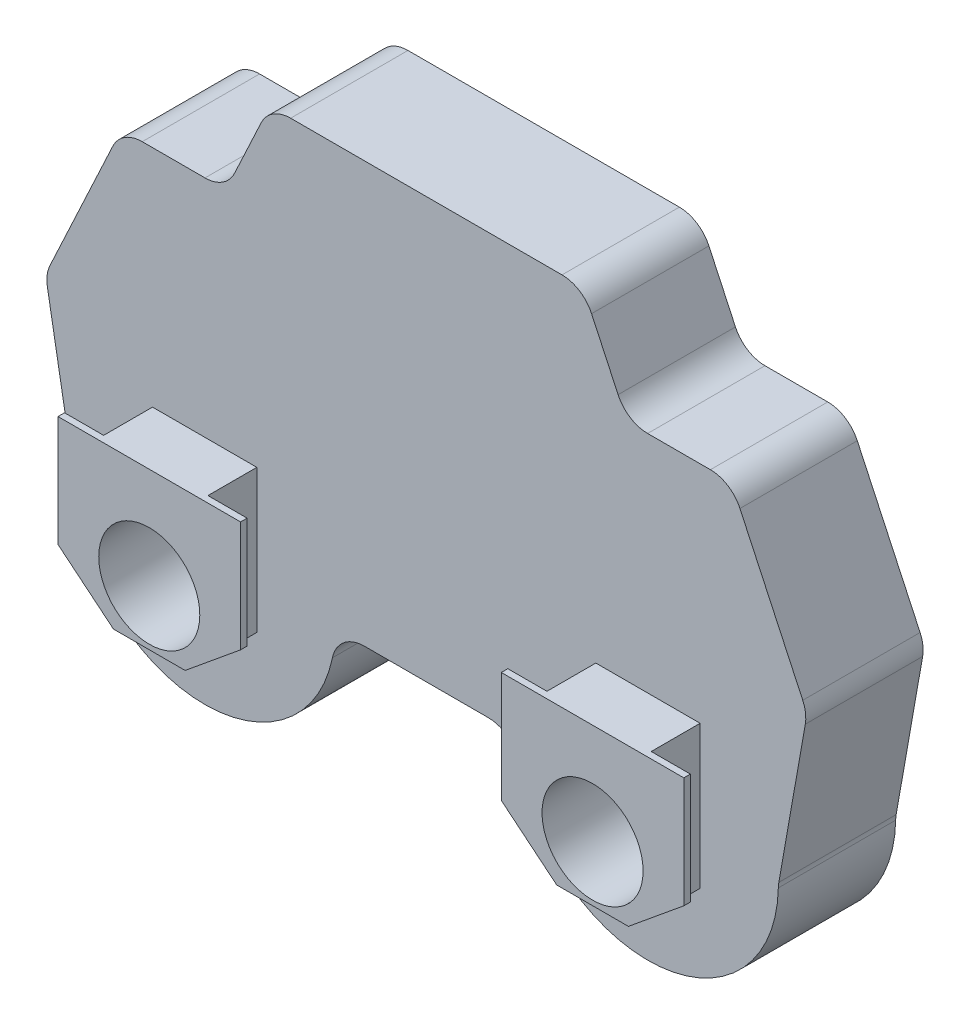
SolidWorks part; units mm, degrees
ref_plane "Alzado" through (0, 0, 0) normal (0, 0, 1) x (1, 0, 0)
ref_plane "Planta" through (0, 0, 0) normal (0, 1, 0) x (1, 0, 0)
ref_plane "Vista lateral" through (0, 0, 0) normal (1, 0, 0) x (0, 0, -1)
sketch "Croquis1" plane through (0, 0, 0) normal (0, 0, 1) x (1, 0, 0)
  line L0 (-9.5051, 0) -> (9.5051, 0)
  line L1 (54.0717, 0.4066) -> (58.1344, 23.4475)
  line L2 (57.7419, 26.4288) -> (48.1081, 47.0886)
  line L3 (43.5765, 49.9755) -> (33.9472, 49.9755)
  line L4 (29.4157, 52.8624) -> (25.3462, 61.5895)
  line L5 (20.8146, 64.4765) -> (-20.8146, 64.4765)
  line L6 (0, 64.4765) -> (0, 0) construction
  line L7 (-29.4157, 52.8624) -> (-25.3462, 61.5895)
  line L8 (-43.5765, 49.9755) -> (-33.9472, 49.9755)
  line L9 (-57.7419, 26.4288) -> (-48.1081, 47.0886)
  line L10 (-54.0717, 0.4066) -> (-58.1344, 23.4475)
  arc A0 (14.4041, -4) -> (53.9966, -0.3693) centre (34, 0) ccw
  arc A1 (58.1344, 23.4475) -> (57.7419, 26.4288) centre (53.2104, 24.3157) ccw
  arc A2 (48.1081, 47.0886) -> (43.5765, 49.9755) centre (43.5765, 44.9755) ccw
  arc A3 (33.9472, 49.9755) -> (29.4157, 52.8624) centre (33.9472, 54.9755) cw
  arc A4 (53.9966, -0.3693) -> (54.0717, 0.4066) centre (58.9957, -0.4616) cw
  arc A5 (9.5051, 0) -> (14.4041, -4) centre (9.5051, -5) cw
  arc A6 (25.3462, 61.5895) -> (20.8146, 64.4765) centre (20.8146, 59.4765) ccw
  circle A7 centre (34, 0) radius 5.5
  circle A8 centre (-34, 0) radius 5.5
  arc A9 (-25.3462, 61.5895) -> (-20.8146, 64.4765) centre (-20.8146, 59.4765) cw
  arc A10 (-9.5051, 0) -> (-14.4041, -4) centre (-9.5051, -5) ccw
  arc A11 (-53.9966, -0.3693) -> (-54.0717, 0.4066) centre (-58.9957, -0.4616) ccw
  arc A12 (-33.9472, 49.9755) -> (-29.4157, 52.8624) centre (-33.9472, 54.9755) ccw
  arc A13 (-48.1081, 47.0886) -> (-43.5765, 49.9755) centre (-43.5765, 44.9755) cw
  arc A14 (-58.1344, 23.4475) -> (-57.7419, 26.4288) centre (-53.2104, 24.3157) cw
  arc A15 (-14.4041, -4) -> (-53.9966, -0.3693) centre (-34, 0) cw
  point P15 (58.4082, 25)
  point P18 (46.7619, 49.9755)
  point P21 (30.7619, 49.9755)
  point P24 (54, 0)
  point P27 (14, 0)
  point P30 (24, 64.4765)
  point P49 (-24, 64.4765)
  point P50 (-14, 0)
  point P51 (-54, 0)
  point P52 (-30.7619, 49.9755)
  point P53 (-46.7619, 49.9755)
  point P54 (-58.4082, 25)
  dimension "D1" = 20
  dimension "D11" = 5
  dimension "D12" = 5
  dimension "D13" = 5
  dimension "D14" = 5
  dimension "D15" = 11
  dimension "D2" = 25
  dimension "D3" = 80
  dimension "D4" = 27.5575
  dimension "D5" = 145
  dimension "D6" = 24
  dimension "D7" = 14
  dimension "D8" = 16
  dimension "D9" = 16
  dimension "D10" = 64.4765
  dimension "D16" = 41.6293
extrude "Saliente-Extruir1" add sketch "Croquis1" along normal blind 18
sketch "Croquis2" plane through (0, 0, 18) normal (0, 0, 1) x (1, 0, 0)
  line L0 (-48.0001, 15.502) -> (-19.9999, 15.502)
  line L1 (19.9999, -1.498) -> (19.9999, 15.502)
  line L2 (28.5, -8.48) -> (19.9999, -1.498)
  line L3 (19.9999, 15.502) -> (48.0001, 15.502)
  line L6 (28.5, -8.48) -> (39.5, -8.48)
  line L7 (-39.5, -8.48) -> (-28.5, -8.48)
  line L9 (39.5, -8.48) -> (48.0001, -1.498)
  line L10 (48.0001, -1.498) -> (48.0001, 15.502)
  line L11 (0, 0) -> (0, 25.1066) construction
  line L12 (-48.0001, -1.498) -> (-48.0001, 15.502)
  line L13 (-39.5, -8.48) -> (-48.0001, -1.498)
  line L18 (-28.5, -8.48) -> (-19.9999, -1.498)
  line L19 (-19.9999, -1.498) -> (-19.9999, 15.502)
  circle A1 centre (34, 0) radius 7.75
  circle A3 centre (-34, 0) radius 7.75
  circle M2 centre (-34, 0) radius 5.5
  circle M27 centre (34, 0) radius 5.5
  dimension "D4" = 15.5
  dimension "D1" = 8.48
  dimension "D2" = 15.502
  dimension "D3" = 11
  dimension "D6" = 17
  dimension "D8" = 11
  dimension "D9" = 17
  dimension "D10" = 14.0001
  dimension "D11" = 14.0001
  dimension "D12" = 10.0438
extrude "Cortar-Extruir1" cut sketch "Croquis2" against normal through all and the other way through all contours A3 M2 | A1 M27 region at (26.4692, 0, 18) region at (-41.5308, 0, 18)
extrude "Saliente-Extruir2" add sketch "Croquis2<6>" along normal blind 8.5
sketch "Croquis2<6>" plane through (0, 0, 18) normal (0, 0, 1) x (1, 0, 0) same geometry as "Croquis2"
sketch "Croquis4" plane through (19.9999, 0, 0) normal (-1, 0, 0) x (0, 0, 1)
  line L0 (26.5, -1.498) -> (26.5, -8.48) construction
  line L1 (18, 15.502) -> (25.5, 15.502)
  line L2 (18, 15.502) -> (18, -7.48)
  line L3 (18, -7.48) -> (25.5, -7.48)
  line L4 (25.5, 15.502) -> (25.5, -7.48)
  line L5 (26.5, -8.48) -> (18, -8.48) construction
  dimension "D1" = 1
  dimension "D2" = 1
  dimension "D3" = 7.5
extrude "Cortar-Extruir2" cut sketch "Croquis4" against normal blind 6
sketch "Croquis5" plane through (48.0001, 0, 0) normal (1, 0, 0) x (0, 0, -1)
  line L0 (-26.5, -1.498) -> (-26.5, 15.502) construction
  line L1 (-18, 15.502) -> (-25.5, 15.502)
  line L2 (-18, 15.502) -> (-18, -7.48)
  line L3 (-18, -7.48) -> (-25.5, -7.48)
  line L4 (-25.5, 15.502) -> (-25.5, -7.48)
  line L5 (-26.5, -8.48) -> (-18, -8.48) construction
  dimension "D1" = 1
  dimension "D2" = 1
extrude "Cortar-Extruir3" cut sketch "Croquis5" against normal blind 6
mirror "Simetría1" about plane through (0, 0, 0) normal (1, 0, 0) of "Cortar-Extruir3", "Cortar-Extruir2"
sketch "Croquis6" plane through (0, 0, 18) normal (0, 0, 1) x (1, 0, 0)
  line L0 (0, 0) -> (0, 43.2309) construction
  line L1 (-15.9544, -10.2809) -> (-51.9544, -10.2809)
  line L2 (15.9544, 19.7191) -> (51.9544, 19.7191)
  line L3 (15.9544, 19.7191) -> (15.9544, -10.2809)
  line L4 (15.9544, -10.2809) -> (51.9544, -10.2809)
  line L5 (51.9544, 19.7191) -> (51.9544, -10.2809)
  line L6 (-51.9544, 19.7191) -> (-51.9544, -10.2809)
  line L7 (-15.9544, 19.7191) -> (-51.9544, 19.7191)
  line L8 (-15.9544, 19.7191) -> (-15.9544, -10.2809)
  dimension "D1" = 36
  dimension "D2" = 30
  dimension "D3" = 15.9544
